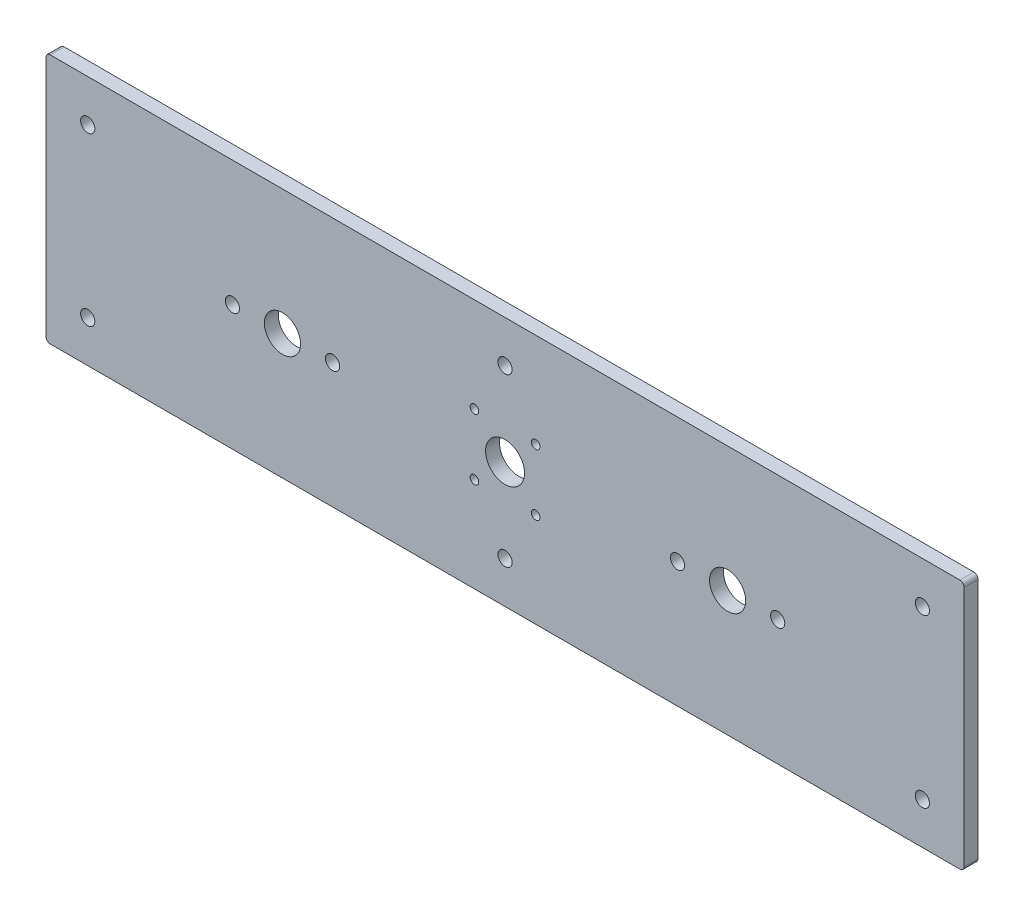
SolidWorks part; units mm, degrees
ref_plane "Front Plane" through (0, 0, 0) normal (0, 0, 1) x (1, 0, 0)
ref_plane "Top Plane" through (0, 0, 0) normal (0, 1, 0) x (1, 0, 0)
ref_plane "Right Plane" through (0, 0, 0) normal (1, 0, 0) x (0, 0, -1)
sketch "Sketch1" plane through (0, 0, 0) normal (0, 0, 1) x (1, 0, 0)
  line L1 (-165, -45) -> (165, -45)
  line L2 (-165, -45) -> (-165, 45)
  line L3 (-165, 45) -> (165, 45)
  line L4 (165, -45) -> (165, 45)
  line L5 (-165, -45) -> (165, 45) construction
  line L6 (-165, 45) -> (165, -45) construction
  point P0 (0, 0)
  dimension "D1" = 330
  dimension "D2" = 90
extrude "Boss-Extrude1" add sketch "Sketch1" along normal mid plane 5
sketch "Sketch2" plane through (0, 0, 2.5) normal (0, 0, 1) x (1, 0, 0)
  line L3 (165, 30) -> (-165, 30)
  line L4 (165, 30) -> (-165, 30) construction
  line L6 (-150, 45) -> (-150, -45)
  line L7 (-150, 45) -> (-150, -45) construction
  line L9 (-165, -30) -> (165, -30)
  line L10 (-165, -30) -> (165, -30) construction
  line L11 (0, 45) -> (0, -45) construction
  line L12 (150, -45) -> (150, 45)
  line L13 (150, -45) -> (150, 45) construction
  line L14 (165, 45) -> (-165, 45) construction
  line L15 (-165, -45) -> (165, -45) construction
  circle A0 centre (150, 30) radius 2.55
  circle A1 centre (150, -30) radius 2.55
  circle A2 centre (0, 30) radius 2.55
  circle A3 centre (0, -30) radius 2.55
  circle A4 centre (-150, -30) radius 2.55
  circle A5 centre (-150, 30) radius 2.55
  dimension "D5" = 5.1
  dimension "D6" = 5.1
  dimension "D7" = 5.1
  dimension "D8" = 5.1
  dimension "D9" = 5.1
  dimension "D10" = 5.1
  dimension "D1" = 15
  dimension "D2" = 15
  dimension "D3" = 15
  dimension "D4" = 15
extrude "Cut-Extrude1" cut sketch "Sketch2" against normal through all
sketch "Sketch3" plane through (0, 0, 2.5) normal (0, 0, 1) x (1, 0, 0)
  line L0 (-165, 0) -> (165, 0) construction
  line L1 (-165, 45) -> (-165, -45) construction
  line L2 (165, -45) -> (165, 45) construction
  circle A0 centre (-80, 0) radius 6.5
  circle A1 centre (-62, 0) radius 2.55
  circle A2 centre (-98, 0) radius 2.55
  dimension "D1" = 13
  dimension "D2" = 5.1
  dimension "D4" = 5.1
  dimension "D3" = 80
  dimension "D5" = 18
  dimension "D6" = 18
extrude "Cut-Extrude2" cut sketch "Sketch3" against normal through all
mirror "Mirror1" about plane through (0, 0, 0) normal (1, 0, 0) of "Cut-Extrude2"
sketch "Sketch4" plane through (0, 0, 2.5) normal (0, 0, 1) x (1, 0, 0)
  line L1 (-11, -11) -> (11, -11) construction
  line L2 (-11, -11) -> (-11, 11) construction
  line L3 (-11, 11) -> (11, 11) construction
  line L4 (11, -11) -> (11, 11) construction
  line L5 (-11, -11) -> (11, 11) construction
  line L6 (-11, 11) -> (11, -11) construction
  circle A0 centre (11, 11) radius 1.55
  circle A1 centre (11, -11) radius 1.55
  circle A2 centre (-11, -11) radius 1.55
  circle A3 centre (-11, 11) radius 1.55
  circle A4 centre (0, 0) radius 7
  point P0 (0, 0)
  dimension "D3" = 3.1
  dimension "D4" = 3.1
  dimension "D5" = 3.1
  dimension "D6" = 3.1
  dimension "D7" = 14
  dimension "D1" = 22
  dimension "D2" = 22
extrude "Cut-Extrude3" cut sketch "Sketch4" against normal through all
fillet "Fillet1" radius 1.5 4 edges at (-165, -45, 0) (-165, 45, 0) (165, -45, 0) (165, 45, 0)
equation "\"D3@Sketch3\"=160/2"
